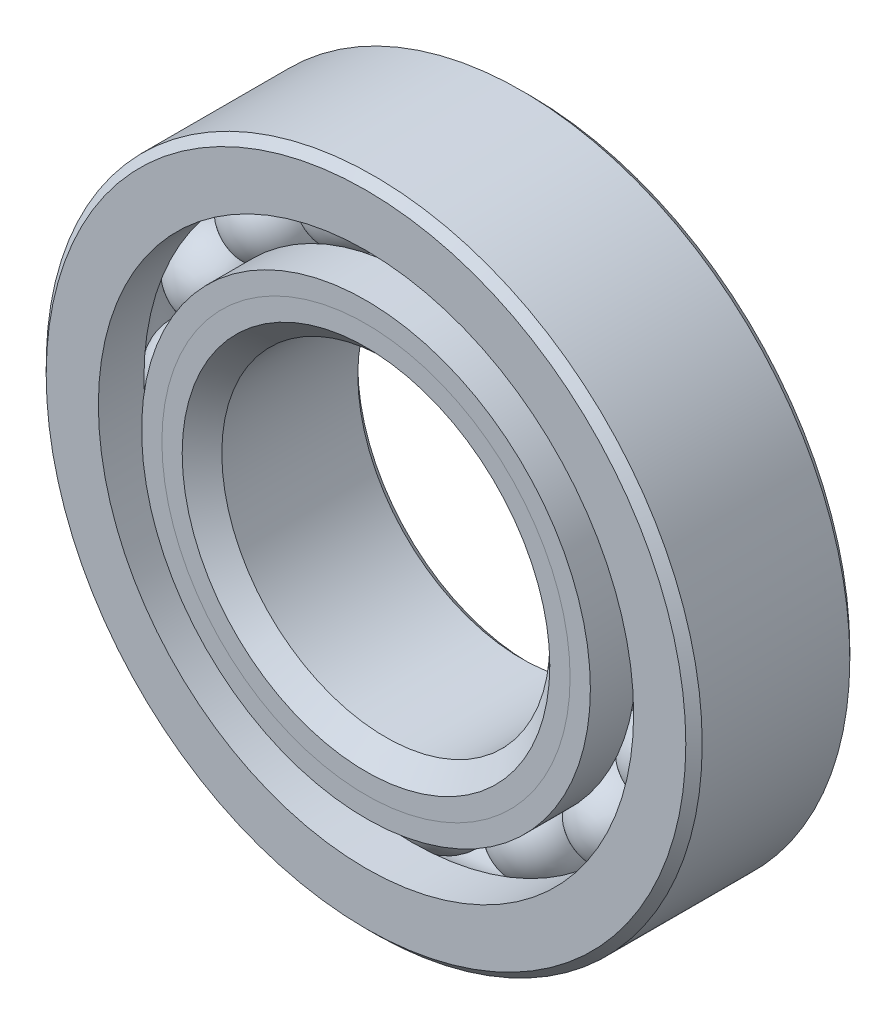
SolidWorks part; units mm, degrees
ref_plane "Front Plane" through (0, 0, 0) normal (0, 0, 1) x (1, 0, 0)
ref_plane "Top Plane" through (0, 0, 0) normal (0, 1, 0) x (1, 0, 0)
ref_plane "Right Plane" through (0, 0, 0) normal (1, 0, 0) x (0, 0, -1)
sketch "Sketch1" plane through (0, 0, 0) normal (1, 0, 0) x (0, 0, -1)
  line L0 (-1.5875, 0) -> (1.5875, 0) construction
  line L1 (0, 6.35) -> (0, -6.35) construction
  line L2 (1.4288, 6.35) -> (-1.4288, 6.35)
  line L3 (-1.4288, 6.35) -> (-1.5875, 6.1913)
  line L4 (-1.5875, 6.1913) -> (-1.5875, 5.1812)
  line L5 (-1.5875, 5.1812) -> (-0.7056, 5.1812)
  line L6 (1.5875, 5.1812) -> (0.7056, 5.1812)
  line L7 (1.5875, 6.1913) -> (1.5875, 5.1812)
  line L8 (1.4288, 6.35) -> (1.5875, 6.1913)
  line L9 (0, 6.35) -> (0, 4.7625) construction
  line L10 (0, 4.7625) -> (0, 3.175) construction
  arc A0 (-0.7056, 5.1812) -> (0.7056, 5.1812) centre (0, 4.7625) cw
  point P14 (0, 3.175)
  dimension "D3" = 1.4111
  dimension "D1" = 45
  dimension "Width" = 3.175
  dimension "OD" = 12.7
  dimension "D2" = 0.1588
  dimension "Shaft Dia" = 6.35
  dimension "D4" = 0.4187
revolve "Revolve1" add sketch "Sketch1" angle 360 about L0
sketch "Sketch2" plane through (0, 0, 0) normal (1, 0, 0) x (0, 0, -1)
  line L0 (-1.5875, 4.3438) -> (-0.7056, 4.3438)
  line L1 (-1.5875, 6.1913) -> (-1.5875, -6.1913) construction
  line L2 (-1.5875, 4.3438) -> (-1.5875, 3.9512)
  line L3 (-1.5875, 3.9512) -> (-1.1949, 3.5585)
  line L4 (-1.1949, 3.5585) -> (0, 3.5585)
  line L5 (0, 6.35) -> (0, -6.35) construction
  line L6 (0, 3.5585) -> (0, 3.9421)
  line L7 (0, 3.9421) -> (0, 3.175) construction
  line L8 (-1.5875, 4.3438) -> (-1.5875, 3.5585) construction
  line L9 (-1.5875, 3.5585) -> (-1.1949, 3.5585) construction
  arc A0 (-0.7056, 4.3438) -> (0, 3.9421) centre (0, 4.7625) ccw
  arc A1 (0.7056, 5.1812) -> (-0.7056, 5.1812) centre (0, 4.7625) ccw construction
  circle A2 centre (0, 4.7625) radius 0.8204 construction
  dimension "D1" = 45
revolve "Revolve2" add sketch "Sketch2" angle 360 about L0
sketch "Sketch3" plane through (0, 0, 0) normal (1, 0, 0) x (0, 0, -1)
  line L0 (-1.5875, 3.9512) -> (-1.1949, 3.5585)
  line L1 (-1.1949, 3.5585) -> (0, 3.5585)
  line L2 (0, 3.5585) -> (0, 3.9421)
  line L3 (-1.5875, 3.9512) -> (-1.5875, 3.5585)
  line L4 (-1.5875, 4.3438) -> (-1.5875, 3.5585) construction
  line L5 (-1.5875, 3.5585) -> (-1.204, 3.175)
  line L6 (-1.204, 3.175) -> (1.4288, 3.175)
  line L7 (1.4288, 6.35) -> (1.4288, -6.35) construction
  line L8 (1.4288, 3.175) -> (1.5875, 3.3337)
  line L9 (1.5875, -6.1913) -> (1.5875, 6.1913) construction
  line L10 (1.5875, 3.3337) -> (1.5875, 4.3438)
  line L11 (1.5875, 4.3438) -> (0.7056, 4.3438)
  line L13 (1.4288, 6.35) -> (1.5875, 6.1913) construction
  circle A0 centre (0, 4.7625) radius 0.8204 construction
  arc A1 (0.7056, 4.3438) -> (0, 3.9421) centre (0, 4.7625) cw
revolve "Revolve3" add sketch "Sketch3" angle 360 about L0
sketch "Sketch4" plane through (0, 0, 0) normal (1, 0, 0) x (0, 0, -1)
  line L0 (-0.8204, 4.7625) -> (0.8204, 4.7625)
  circle A1 centre (0, 4.7625) radius 0.8204 construction
  arc A2 (-0.8204, 4.7625) -> (0.8204, 4.7625) centre (0, 4.7625) cw
  arc A3 (0.7056, 5.1812) -> (-0.7056, 5.1812) centre (0, 4.7625) ccw construction
revolve "Revolve4" add sketch "Sketch4" angle 360 about L0
ref_axis "Axis1" through (0, 0, -1.5875) along (0, 0, 1)
pattern_circular "CirPattern1" count 16 every 22.5 about axis through (0, 0, -1.5875) along (0, 0, 1) of bodies 104
equation "\"D2@Sketch1\" = \"Width@Sketch1\"*.05"
equation "\"D3@Sketch1\" = \"Width@Sketch1\"/2.25"
equation "\"D4@Sketch1\" = (((\"OD@Sketch1\"-\"Width@Sketch1\")/2)/3.25)/3.5"
equation "\"D2@CirPattern1\" = 360/\"Balls@CirPattern1\""
